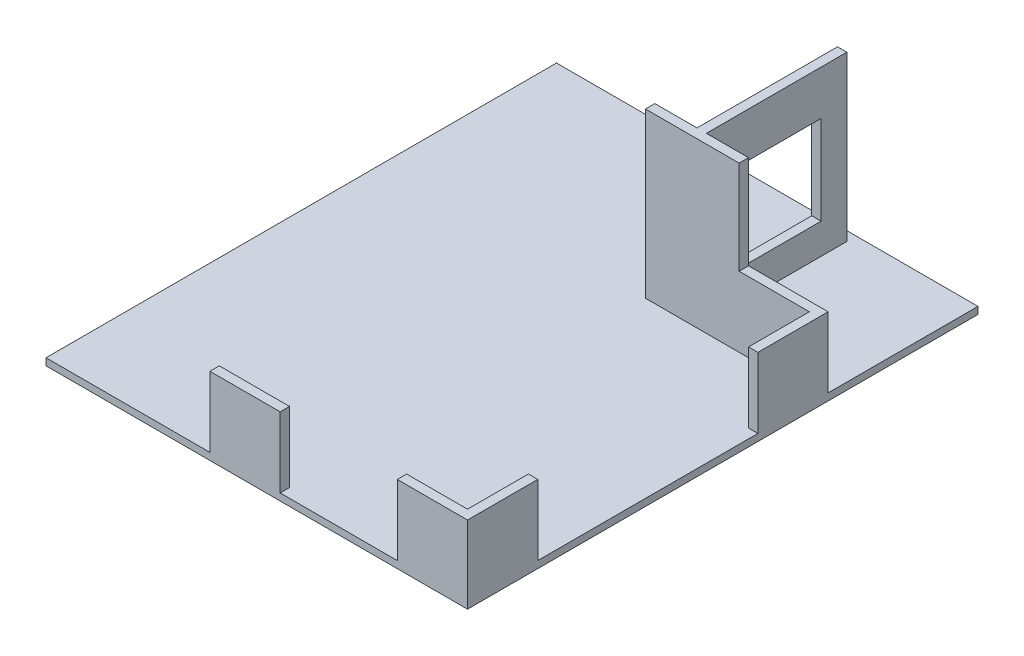
SolidWorks part; units mm, degrees
ref_plane "Front Plane" through (0, 0, 0) normal (0, 0, 1) x (1, 0, 0)
ref_plane "Top Plane" through (0, 0, 0) normal (0, 1, 0) x (1, 0, 0)
ref_plane "Right Plane" through (0, 0, 0) normal (1, 0, 0) x (0, 0, -1)
sketch "Sketch1" plane through (0, 0, 0) normal (0, 1, 0) x (1, 0, 0)
  line L1 (0, 0) -> (180, 0)
  line L2 (0, 0) -> (0, 218)
  line L3 (0, 218) -> (180, 218)
  line L4 (180, 0) -> (180, 218)
  dimension "D1" = 218
  dimension "D2" = 180
extrude "Boss-Extrude1" add sketch "Sketch1" along normal blind 3
sketch "Sketch2" plane through (0, 3, 0) normal (0, 1, 0) x (1, 0, 0)
  line L15 (0, 0) -> (180, 0) construction
  line L16 (70, 0) -> (100, 0)
  line L17 (70, 0) -> (70, 4)
  line L18 (70, 4) -> (100, 4)
  line L19 (100, 0) -> (100, 4)
  line L20 (150, 0) -> (180, 0)
  line L21 (180, 0) -> (180, 30)
  line L22 (180, 0) -> (180, 218) construction
  line L23 (180, 30) -> (176, 30)
  line L24 (176, 30) -> (176, 4)
  line L25 (176, 4) -> (150, 4)
  line L26 (150, 4) -> (150, 0)
  line L27 (180, 124) -> (180, 154)
  line L28 (180, 154) -> (146, 154)
  line L29 (146, 154) -> (146, 150)
  line L30 (146, 150) -> (176, 150)
  line L31 (176, 150) -> (176, 124)
  line L32 (176, 124) -> (180, 124)
  dimension "D1" = 4
  dimension "D2" = 30
  dimension "D3" = 80
  dimension "D4" = 4
  dimension "D5" = 4
  dimension "D6" = 30
  dimension "D7" = 30
  dimension "D8" = 4
  dimension "D9" = 4
  dimension "D10" = 30
  dimension "D11" = 34
  dimension "D12" = 146
extrude "Boss-Extrude2" add sketch "Sketch2" along normal blind 30
sketch "Sketch4" plane through (0, 3, 0) normal (0, 1, 0) x (1, 0, 0)
  line L0 (124, 154) -> (124, 214)
  line L5 (124, 214) -> (128, 214)
  line L6 (128, 214) -> (128, 154)
  line L13 (180, 154) -> (180, 218) construction
  line L15 (124, 154) -> (106, 154)
  line L16 (146, 154) -> (128, 154)
  line L17 (146, 154) -> (146, 150)
  line L18 (146, 150) -> (106, 150)
  line L19 (106, 154) -> (106, 150)
  dimension "D1" = 4
  dimension "D2" = 40
  dimension "D3" = 150
  dimension "D4" = 18
  dimension "D5" = 4
  dimension "D6" = 60
  dimension "D7" = 52
extrude "Boss-Extrude3" add sketch "Sketch4" along normal blind 70
sketch "Sketch5" plane through (128, 0, 0) normal (1, 0, 0) x (0, 0, -1)
  line L0 (154, 3) -> (214, 3) construction
  line L1 (165, 54) -> (203, 54)
  line L2 (165, 54) -> (165, 16)
  line L3 (165, 16) -> (203, 16)
  line L4 (203, 54) -> (203, 16)
  line L5 (154, 73) -> (154, 33) construction
  dimension "D1" = 38
  dimension "D2" = 38
  dimension "D3" = 13
  dimension "D4" = 11
extrude "Cut-Extrude1" cut sketch "Sketch5" against normal blind 10
